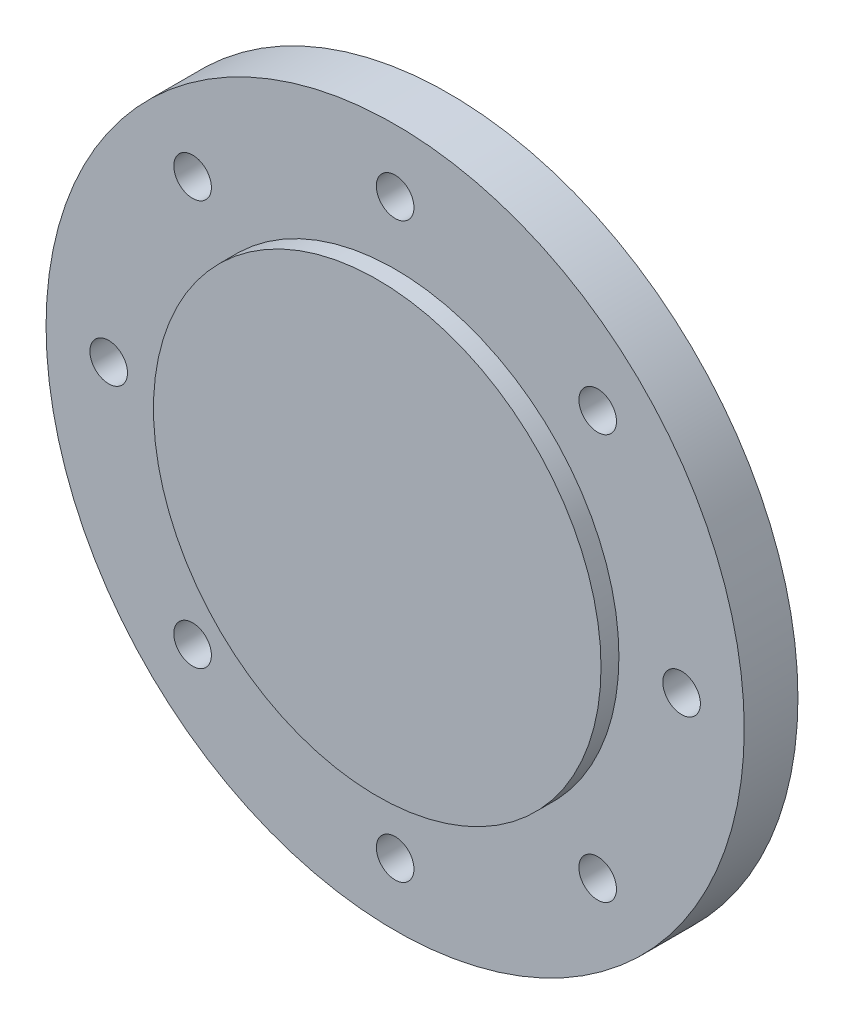
SolidWorks part; units mm, degrees
ref_plane "Front Plane" through (0, 0, 0) normal (0, 0, 1) x (1, 0, 0)
ref_plane "Top Plane" through (0, 0, 0) normal (0, 1, 0) x (1, 0, 0)
ref_plane "Right Plane" through (0, 0, 0) normal (1, 0, 0) x (0, 0, -1)
sketch "SK_Disc" plane through (0, 0, 0) normal (0, 0, 1) x (1, 0, 0)
  circle A0 centre (0, 0) radius 39
  dimension "D_disc" = 78
extrude "Output_Disc" add sketch "SK_Disc" along normal blind 6
ref_plane "PL_Mount" through (0, 0, 6) normal (0, 0, 1) x (1, 0, 0)
sketch "SK_Pilot" plane through (0, 0, 6) normal (0, 0, 1) x (1, 0, 0)
  circle A0 centre (0, 0) radius 25
  dimension "D_pil" = 50
extrude "Pilot_Boss" add sketch "SK_Pilot" along normal blind 2
sketch "SK_OutHole" plane through (0, 0, 6) normal (0, 0, 1) x (1, 0, 0)
  circle A0 centre (32, 0) radius 2.1
  dimension "D_oh" = 4.2
  dimension "R_oh" = 32
extrude "Output_Tapped_Hole" cut sketch "SK_OutHole" against normal blind 6
ref_axis "AX_Joint" through (0, 0, -0.4) along (0, 0, 1)
pattern_circular "Output_Hole_Pattern" count 8 over 360 about axis through (0, 0, -0.4) along (0, 0, 1) of "Output_Tapped_Hole"
equation "\"D_out\" = 78"
equation "\"T_out\" = 6"
equation "\"PCD_out\" = 64"
equation "\"D_pilot\" = 50"
equation "\"H_pilot\" = 2"
equation "\"D_out_hole\" = 4.2"
equation "\"D_disc@SK_Disc\" = \"D_out\""
equation "\"D1@Output_Disc\" = \"T_out\""
equation "\"D_pil@SK_Pilot\" = \"D_pilot\""
equation "\"D1@Pilot_Boss\" = \"H_pilot\""
equation "\"D_oh@SK_OutHole\" = \"D_out_hole\""
equation "\"R_oh@SK_OutHole\" = \"PCD_out\"/2"
